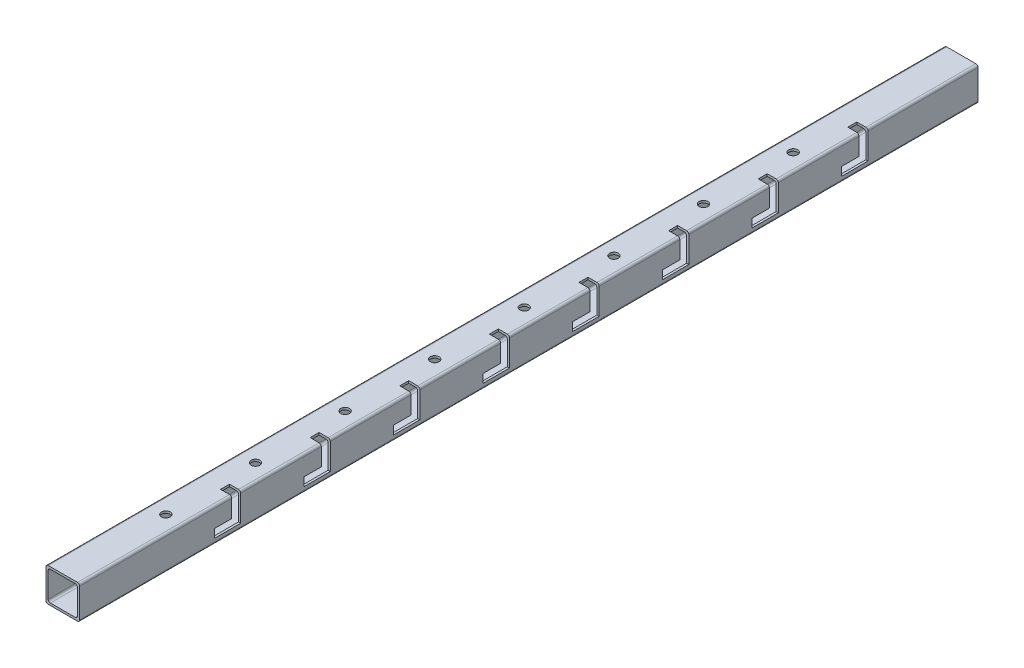
SolidWorks part; units mm, degrees
ref_plane "Front Plane" through (0, 0, 0) normal (0, 0, 1) x (1, 0, 0)
ref_plane "Top Plane" through (0, 0, 0) normal (0, 1, 0) x (1, 0, 0)
ref_plane "Right Plane" through (0, 0, 0) normal (1, 0, 0) x (0, 0, -1)
sketch "Sketch1" plane through (0, 0, 0) normal (0, 0, 1) x (1, 0, 0)
  line L0 (-9.525, 0) -> (9.525, 0) construction
  line L1 (0, -9.525) -> (0, 9.525) construction
  line L2 (8.2804, 0) -> (8.2804, 8.2804) construction
  line L3 (-9.525, -9.525) -> (9.525, -9.525) construction
  line L4 (-9.525, -9.525) -> (-9.525, 9.525) construction
  line L5 (-9.525, 9.525) -> (9.525, 9.525) construction
  line L6 (9.525, -9.525) -> (9.525, 9.525) construction
  line L7 (-9.525, -9.525) -> (9.525, 9.525) construction
  line L8 (-9.525, 9.525) -> (9.525, -9.525) construction
  line L9 (8.2804, 8.2804) -> (-8.2804, 8.2804) construction
  line L10 (-8.2804, 8.2804) -> (-8.2804, -8.2804) construction
  line L11 (-8.2804, -8.2804) -> (8.2804, -8.2804) construction
  line L12 (8.2804, -8.2804) -> (8.2804, 0) construction
  point P0 (0, 0)
  point P4 (0, 0)
  point P9 (0, 0)
  point P10 (8.2804, 0)
  point P13 (0, -8.2804)
  point P14 (-8.2804, 0)
  point P15 (0, 8.2804)
  dimension "Width" = 19.05
  dimension "Wall Thickness" = 1.2446
  dimension "Height" = 19.05
  dimension "D1" = 1.2446
  dimension "D2" = 1.2446
  dimension "D3" = 1.2446
sketch "Sketch2" plane through (0, 0, 0) normal (1, 0, 0) x (0, 0, -1)
  line L0 (254.635, 9.525) -> (-254.635, 9.525) construction
  point P3 (-232.7275, 9.525)
  point P5 (232.7275, 9.525)
  point P7 (0, 9.525)
  dimension "D1" = 21.9075
  dimension "D2" = 21.9075
  dimension "Length" = 509.27
sketch "Sketch3" plane through (0, 0, 0) normal (0, 0, 1) x (1, 0, 0)
  line L1 (9.525, 9.525) -> (-9.525, 9.525)
  line L2 (-9.525, 9.525) -> (-9.525, -9.525)
  line L3 (-9.525, -9.525) -> (9.525, -9.525) construction
  line L4 (-9.525, -9.525) -> (9.525, -9.525)
  line L5 (9.525, -9.525) -> (9.525, 9.525)
  line L6 (-8.2804, 8.2804) -> (8.2804, 8.2804)
  line L7 (8.2804, 8.2804) -> (8.2804, -8.2804)
  line L8 (8.2804, -8.2804) -> (-8.2804, -8.2804)
  line L9 (-8.2804, -8.2804) -> (-8.2804, 8.2804)
extrude "Boss-Extrude1" add sketch "Sketch3" along normal mid plane 509.27
fillet "Fillet1" radius 1.2446 8 edges at (-9.525, 9.525, 0) (8.2804, -8.2804, 0) (-8.2804, -8.2804, 0) (-8.2804, 8.2804, 0) (8.2804, 8.2804, 0) (9.525, -9.525, 0) (-9.525, -9.525, 0) (9.525, 9.525, 0)
sketch "Sketch4" plane through (0, 9.525, 0) normal (0, 1, 0) x (1, 0, 0)
  line L0 (0, 254.635) -> (0, 159.385) construction
  line L1 (8.2804, 254.635) -> (-8.2804, 254.635) construction
  line L2 (0, 159.385) -> (0, 108.585) construction
  circle A0 centre (0, 159.385) radius 2.4892
  circle A1 centre (0, 108.585) radius 2.4892
  circle A2 centre (0, 57.785) radius 2.4892
  circle A3 centre (0, 6.985) radius 2.4892
  circle A4 centre (0, -43.815) radius 2.4892
  circle A5 centre (0, -94.615) radius 2.4892
  circle A6 centre (0, -145.415) radius 2.4892
  circle A7 centre (0, -196.215) radius 2.4892
  dimension "D2" = 4.9784
  dimension "D4" = 4.9784
  dimension "D1" = 95.25
  dimension "D3" = 50.8
  dimension "D5" = 7
extrude "Cut-Extrude1" cut sketch "Sketch4" against normal through all
sketch "Sketch6" plane through (-9.525, 0, 0) normal (-1, 0, 0) x (0, 0, 1)
  line L0 (-254.635, 0) -> (-179.705, 0) construction
  line L1 (-254.635, 8.2804) -> (-254.635, -8.2804) construction
  line L2 (-182.118, -1.651) -> (-187.198, -1.651)
  line L7 (-182.118, -6.477) -> (-177.292, -1.651) construction
  line L12 (-177.292, -6.477) -> (-182.118, -6.477)
  line L13 (-177.292, -6.477) -> (-177.292, -1.651)
  line L14 (-177.292, -1.651) -> (-182.118, -1.651)
  line L15 (-182.118, -6.477) -> (-182.118, -1.651) construction
  line L16 (-192.278, 9.525) -> (-192.278, -6.477)
  line L17 (-177.292, -6.477) -> (-182.118, -1.651) construction
  line L18 (-254.635, 9.525) -> (254.635, 9.525) construction
  line L19 (-192.278, -6.477) -> (-182.118, -6.477)
  line L20 (-187.198, -1.651) -> (-187.198, 9.525)
  line L21 (-187.198, 9.525) -> (-192.278, 9.525)
  point P12 (-179.705, -4.064)
  dimension "D1" = 74.93
  dimension "D2" = 16.002
  dimension "D3" = 4.826
  dimension "D4" = 4.826
  dimension "D5" = 10.16
  dimension "D6" = 5.08
extrude "Cut-Extrude3" cut sketch "Sketch6" along normal blind 6.35 from surface starting at face at (9.525, 0, 0)
pattern_linear "LPattern2" count 8 spacing 50.8 along (0, 0, 1) of "Cut-Extrude3"
equation "\"D1@Boss-Extrude1\" = \"Length@Sketch2\""
equation "\"D1@Sketch2\" = \"Width@Sketch1\" * 1.15"
equation "\"D2@Sketch2\"=\"D1@Sketch2\""
equation "\"D1@Sketch1\"=\"Wall Thickness@Sketch1\""
equation "\"D2@Sketch1\"=\"Wall Thickness@Sketch1\""
equation "\"D3@Sketch1\"=\"Wall Thickness@Sketch1\""
equation "\"D1@Fillet1\"=\"Wall Thickness@Sketch1\""
